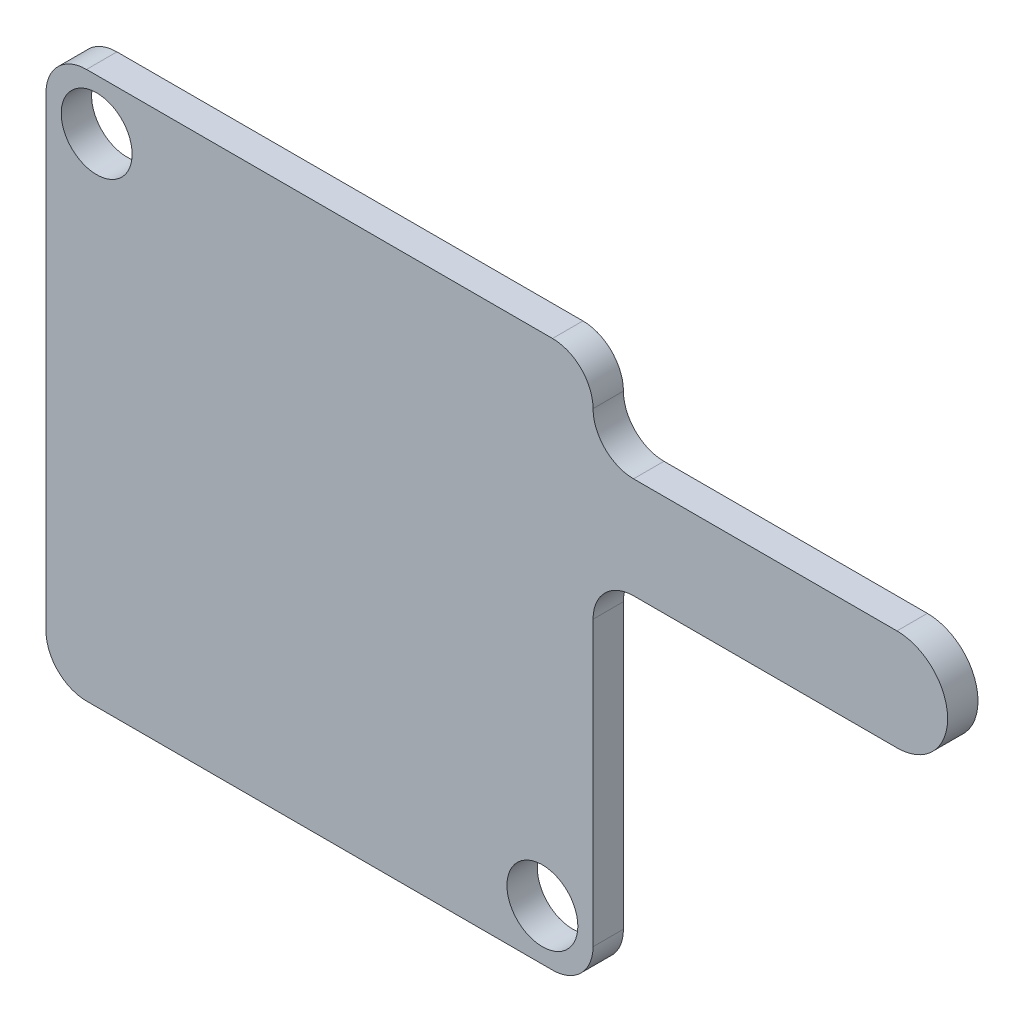
SolidWorks part; units mm, degrees
material "Alliage 1060"
ref_plane "Face" through (0, 0, 0) normal (0, 0, 1) x (1, 0, 0)
ref_plane "Dessus" through (0, 0, 0) normal (0, 1, 0) x (1, 0, 0)
ref_plane "Droite" through (0, 0, 0) normal (1, 0, 0) x (0, 0, -1)
sketch "Esquisse1" plane through (0, 0, 0) normal (0, 0, 1) x (1, 0, 0)
  line L0 (2.5, 27) -> (2.5, 0) construction
  line L1 (0, 0) -> (27, 0)
  line L2 (0, 0) -> (0, 27)
  line L3 (0, 27) -> (27, 27)
  line L4 (27, 0) -> (27, 18)
  line L5 (24.5, 27) -> (24.5, 0) construction
  line L6 (0, 24.5) -> (27, 24.5) construction
  line L7 (0, 2.5) -> (27, 2.5) construction
  line L8 (27, 23) -> (42, 23)
  line L10 (42, 18) -> (27, 18)
  line L11 (27, 23) -> (27, 27)
  circle A0 centre (2.5, 24.5) radius 1.75
  circle A1 centre (24.5, 2.5) radius 1.75
  arc A2 (42, 23) -> (42, 18) centre (42, 20.5) cw
  point P21 (27, 0)
  point P24 (0, 0)
  point P27 (0, 27)
  dimension "D7" = 3.5
  dimension "D11" = 3.5
  dimension "D1" = 2.5
  dimension "D2" = 27
  dimension "D3" = 27
  dimension "D4" = 22
  dimension "D5" = 2.5
  dimension "D6" = 22
  dimension "D8" = 4
  dimension "D9" = 5
  dimension "D10" = 15
extrude "Boss.-Extru.1" add sketch "Esquisse1" along normal blind 1.5
fillet "Congé1" radius 2 6 edges at (0, 0, 0.75) (27, 18, 0.75) (27, 0, 0.75) (0, 27, 0.75) (27, 27, 0.75) (27, 23, 0.75)
